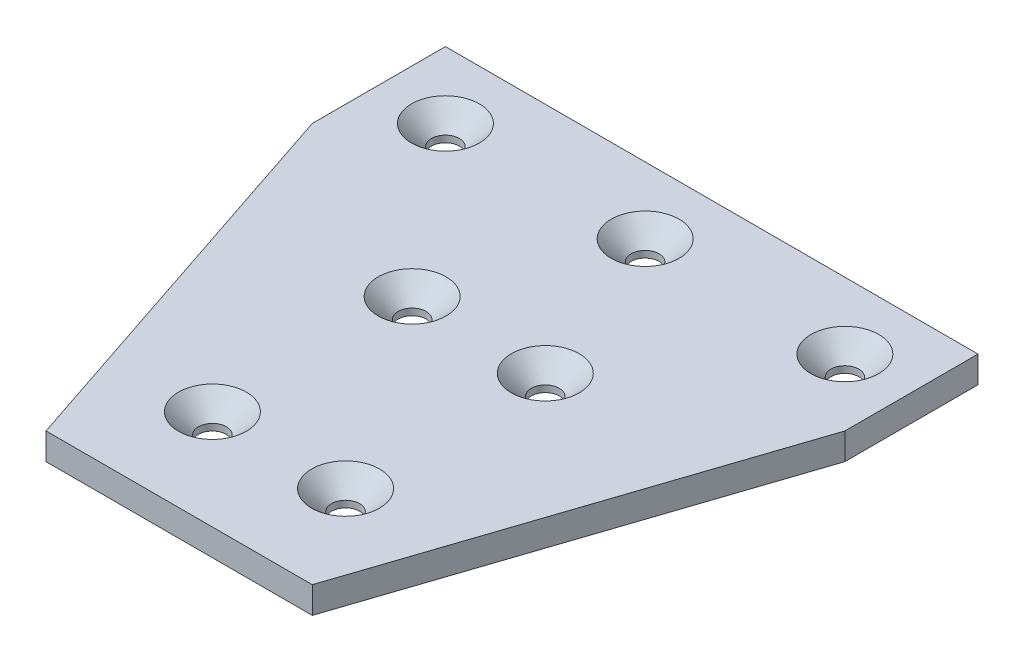
SolidWorks part; units mm, degrees
ref_plane "Front Plane" through (0, 0, 0) normal (0, 0, 1) x (1, 0, 0)
ref_plane "Top Plane" through (0, 0, 0) normal (0, 1, 0) x (1, 0, 0)
ref_plane "Right Plane" through (0, 0, 0) normal (1, 0, 0) x (0, 0, -1)
sketch "Sketch1" plane through (0, 0, 0) normal (0, 1, 0) x (1, 0, 0)
  line L0 (0, -40) -> (0, 0) construction
  line L1 (-40, -10) -> (40, -10)
  line L2 (-40, -10) -> (-40, 10)
  line L3 (-40, 10) -> (40, 10)
  line L4 (40, -10) -> (40, 10)
  line L5 (-40, -10) -> (40, 10) construction
  line L6 (-40, 10) -> (40, -10) construction
  line L7 (-20, -70) -> (20, -70)
  line L8 (-20, -70) -> (-20, -10)
  line L9 (-20, -10) -> (20, -10)
  line L10 (20, -70) -> (20, -10)
  line L11 (-20, -70) -> (20, -10) construction
  line L12 (-20, -10) -> (20, -70) construction
  line L13 (-40, -10) -> (-20, -70)
  line L14 (20, -70) -> (40, -10)
  line L15 (-40, 10) -> (-20, -10) construction
  line L16 (-20, -10) -> (-20, 10) construction
  line L17 (-20, 10) -> (-40, -10) construction
  line L18 (40, 10) -> (20, -10) construction
  line L19 (-10, -40) -> (-10, -25) construction
  line L20 (-10, -40) -> (-10, -55) construction
  line L21 (-10, -40) -> (0, -40) construction
  line L22 (0, -40) -> (10, -40) construction
  line L23 (10, -55) -> (10, -40) construction
  line L24 (10, -40) -> (10, -25) construction
  circle A0 centre (-30, 0) radius 2.1
  circle A1 centre (30, 0) radius 2.1
  circle A2 centre (0, 0) radius 2.1
  circle A3 centre (-10, -25) radius 2.1
  circle A4 centre (10, -25) radius 2.1
  circle A5 centre (10, -55) radius 2.1
  circle A6 centre (-10, -55) radius 2.1
  point P0 (0, 0)
  point P6 (0, -40)
  dimension "D6" = 4.2
  dimension "D1" = 60
  dimension "D2" = 40
  dimension "D3" = 20
  dimension "D4" = 80
  dimension "D5" = 45
  dimension "D7" = 10
extrude "Boss-Extrude1" add sketch "Sketch1" along normal blind 4 contours L7 L10 L1 L8 A6 A5 A4 A3 | L1 L13 L8 | L10 L14 L1 | L1 L4 L3 L2 A2 A1 A0 region at (-39.1754, 0, 0) region at (-26.6667, 0, 30) region at (0, 0, 40) region at (26.6667, 0, 30)
chamfer "Chamfer1" distance 3 angle 45 7 edges at (10, 4, 57.1) (-10, 4, 57.1) (10, 4, 27.1) (-10, 4, 27.1) (30, 4, 2.1) (0, 4, 2.1) (-30, 4, 2.1)
fillet "Fillet1" [suppressed] radius 4
